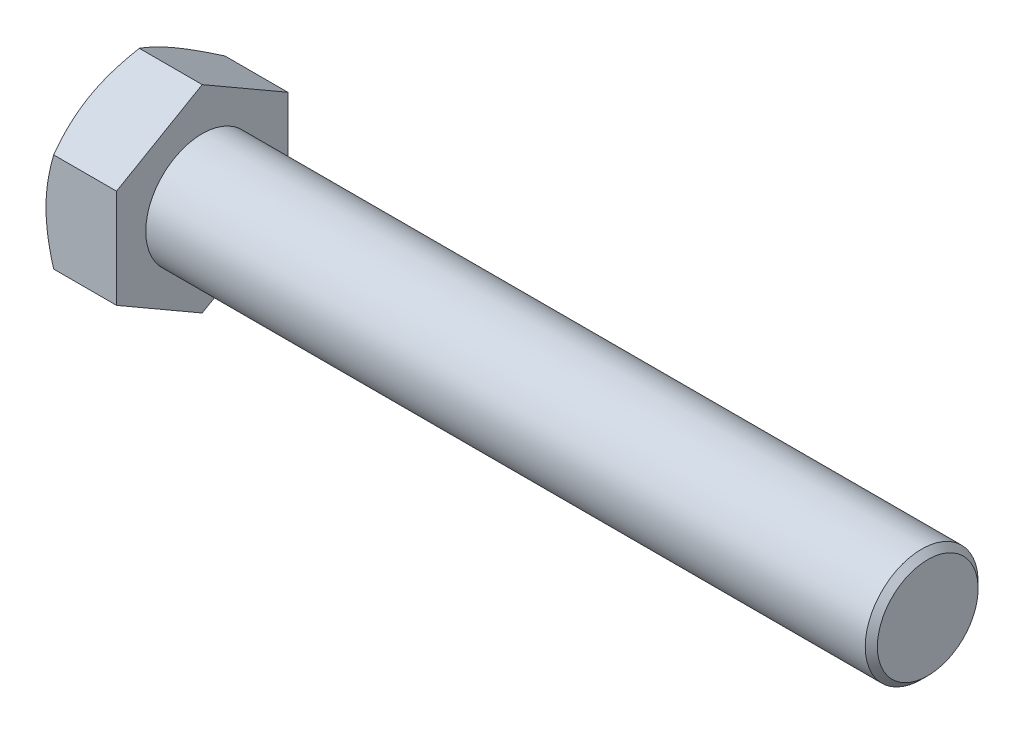
SolidWorks part; units mm, degrees
ref_plane "Front Plane" through (0, 0, 0) normal (0, 0, 1) x (1, 0, 0)
ref_plane "Top Plane" through (0, 0, 0) normal (0, 1, 0) x (1, 0, 0)
ref_plane "Right Plane" through (0, 0, 0) normal (1, 0, 0) x (0, 0, -1)
sketch "BaseHeadSke" plane through (0, 0, 0) normal (1, 0, 0) x (0, 0, -1)
  line L1 (0, 49.0748) -> (-42.5, 24.5374)
  line L2 (-42.5, 24.5374) -> (-42.5, -24.5374)
  line L3 (-42.5, -24.5374) -> (0, -49.0748)
  line L4 (0, -49.0748) -> (42.5, -24.5374)
  line L5 (42.5, -24.5374) -> (42.5, 24.5374)
  line L6 (42.5, 24.5374) -> (0, 49.0748)
  circle A0 centre (0, 0) radius 42.5 construction
extrude "BaseHead" add sketch "BaseHeadSke" along normal blind 35
sketch "HeadChamferSke" plane through (0, 0, 0) normal (0, 0, 1) x (1, 0, 0)
  line L0 (0, 0) -> (108.1848, 0) construction
  line L1 (0, 24.5374) -> (0, -24.5374) construction
  line L2 (0, 49.0748) -> (0, 42.5)
  line L3 (0, 42.5) -> (3.7959, 49.0748)
  line L4 (3.7959, 49.0748) -> (0, 49.0748)
  line L7 (35, 49.0748) -> (0, 49.0748) construction
  dimension "Angle_Chamfer_Head" = 30
revolve "HeadChamfer" cut sketch "HeadChamferSke" angle 360 about L0
sketch "BodySke" plane through (0, 0, 0) normal (0, 0, 1) x (1, 0, 0)
  line L0 (0, 0) -> (440.8544, 0) construction
  line L1 (0, 0) -> (0, 28)
  line L3 (0, 36.8061) -> (0, 0) construction
  line L4 (0, 28) -> (391.9855, 28)
  line L5 (391.9855, 28) -> (395, 24.9855)
  line L6 (395, 24.9855) -> (395, 0)
  line L7 (395, 0) -> (0, 0)
  line L8 (40.5, 0) -> (40.5, 20.794) construction
  line L9 (35, 24.5374) -> (35, -24.5374) construction
  line L10 (35, 0) -> (35, 20.794) construction
  dimension "Thread_minor" = 49.971
  dimension "Advance" = 5.5
revolve "BaseBody" add sketch "BodySke" angle 360 about L0
cosmetic thread "ThreadCosmetic" [suppressed]
sketch "BearingFaceSke" plane through (0, 0, 0) normal (0, 0, 1) x (1, 0, 0)
  line L0 (0, 0) -> (414.2241, 0) construction
  line L1 (35, 49.0748) -> (35, 24.5374) construction
  line L2 (35, 42.5) -> (34, 42.5)
  line L3 (35, 42.5) -> (35, 52.5)
  line L4 (35, 52.5) -> (34, 52.5)
  line L5 (34, 42.5) -> (34, 52.5)
  dimension "D1" = 10
  dimension "D2" = 85
revolve "BearingFace" [suppressed] cut sketch "BearingFaceSke" angle 360 about L0
fillet "HeadFillet" [suppressed] radius 2
sketch "ThdSchSke" plane through (0, 0, 0) normal (0, 0, 1) x (1, 0, 0)
  line L0 (0, 0) -> (453.2163, 0) construction
  line L1 (386.4855, 31.4808) -> (386.4855, 28)
  line L2 (386.4855, 31.4808) -> (389.9663, 31.4808)
  line L3 (389.9663, 31.4808) -> (389.9663, 28)
  line L4 (389.9663, 28) -> (388.2259, 24.9855)
  line L5 (388.2259, 24.9855) -> (386.4855, 28)
  dimension "D1" = 5.5
revolve "ThreadSchematic" [suppressed] cut sketch "ThdSchSke" angle 360 about L0
pattern_linear "ThdSchPat" [suppressed] of bodies 117
equation "\"Thread_minor@ThreadCosmetic\" = \"Thread_minor@BodySke\""
equation "\"D2@BearingFaceSke\" = \"Width_flats@BaseHeadSke\""
equation "\"D1@ThdSchSke\" = \"Advance@BodySke\""
equation "\"Advance@ThdSchPat\" = \"Advance@BodySke\""
equation "\"Tooth_Num@ThdSchPat\" =  int( \"Thread_length@BodySke\" / \"Advance@BodySke\" ) - 1 "
